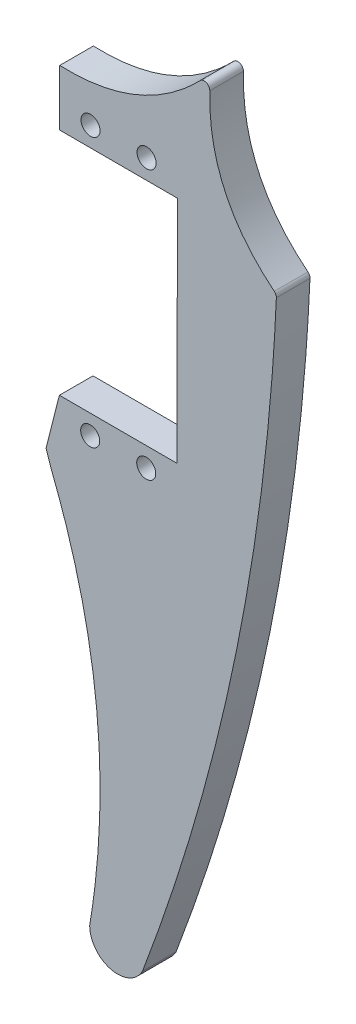
SolidWorks part; units mm, degrees
material "ABS"
ref_plane "Front Plane" through (0, 0, 0) normal (0, 0, 1) x (1, 0, 0)
ref_plane "Top Plane" through (0, 0, 0) normal (0, 1, 0) x (1, 0, 0)
ref_plane "Right Plane" through (0, 0, 0) normal (1, 0, 0) x (0, 0, -1)
sketch "Sketch1" plane through (0, 0, 0) normal (0, 0, 1) x (1, 0, 0)
  line L1 (-25, -73) -> (25, -73)
  line L2 (-25, -73) -> (-25, 73)
  line L3 (-25, 73) -> (25, 73)
  line L4 (25, -73) -> (25, 73)
  line L5 (-25, -73) -> (25, 73) construction
  line L6 (-25, 73) -> (25, -73) construction
  point P0 (0, 0)
  dimension "D1" = 50
  dimension "D2" = 146
extrude "Boss-Extrude1" add sketch "Sketch1" along normal blind 6
sketch "Sketch3" plane through (0, 0, 6) normal (0, 0, 1) x (1, 0, 0)
  line L0 (-18.1577, 62.4611) -> (-18.1698, 52.4611)
  line L1 (-18.1698, 52.4611) -> (2.8301, 52.4355)
  line L2 (2.8301, 52.4355) -> (2.7802, 11.4356)
  line L3 (2.7802, 11.4356) -> (-18.2198, 11.4611)
  line L4 (-18.2198, 11.4611) -> (-20.6029, 2.0952)
  line L5 (-25, 73) -> (25, 73)
  line L6 (25, 73) -> (25, -73)
  line L7 (25, -73) -> (-25, -73)
  line L8 (-25, -73) -> (-25, 73)
  circle A0 centre (-12.724, 7.9545) radius 1.7
  circle A1 centre (-2.724, 7.9423) radius 1.7
  circle A2 centre (-12.6656, 55.9544) radius 1.7
  circle A3 centre (-2.6656, 55.9422) radius 1.7
  arc A4 (6.9003, 72.6534) -> (8.6175, 71.93) centre (7.6179, 71.9569) cw
  arc A5 (20.1233, 46.7018) -> (20.4934, 45.8805) centre (19.4944, 45.9243) cw
  arc A6 (20.4944, 45.9231) -> (20.1233, 46.7018) centre (19.4944, 45.9243) ccw construction
  arc A7 (-12.8163, -67.7955) -> (-3.3861, -70.1197) centre (-7.8163, -67.8016) ccw
  arc A8 (-12.8163, -67.7955) -> (-3.3861, -70.1197) centre (-7.8163, -67.8016) ccw construction
  spline S0 degree 2 poles (8.6175, 71.93) (8.1984, 56.3487) (20.1233, 46.7018) knots 0.080015 0.080015 0.080015 0.985244 0.985244 0.985244 weights 1 1 1 construction
  spline S1 degree 3 poles (-20.6029, 2.0952) (-20.0205, 0.1176) (-18.5975, -3.3343) (-16.9042, -8.2632) (-15.5957, -12.5461) (-14.4561, -16.8104) (-13.503, -20.9757) (-12.4751, -26.3756) (-11.593, -32.6604) (-10.8025, -42.8899) (-11.0088, -54.6421) (-12.1531, -63.8384) (-12.8163, -67.7955) knots 0 0 0 0 0.086646 0.157135 0.219373 0.275195 0.342966 0.399252 0.506628 0.609998 0.831095 1 1 1 1
  spline S2 degree 2 poles (-20.5559, 1.4618) (-6.7301, -31.4908) (-12.8163, -67.7955) knots 0.004655 0.004655 0.004655 1 1 1 weights 1 1 1 construction
  spline S3 degree 3 poles (-3.3861, -70.1197) (-2.2175, -67.0295) (-0.1824, -61.4321) (2.3206, -54.0109) (4.3961, -47.472) (6.0842, -41.8268) (7.7734, -35.8279) (9.3145, -30.0063) (10.8472, -23.7774) (12.2485, -17.634) (13.3818, -12.2462) (14.4459, -6.8132) (15.4509, -1.2735) (16.5413, 5.3978) (17.5258, 12.2275) (18.3183, 18.5775) (18.9682, 24.556) (19.5468, 30.7474) (20.0911, 37.9797) (20.3738, 43.1533) (20.4934, 45.8805) knots 0 0 0 0 0.083335 0.150214 0.197536 0.256374 0.298828 0.354729 0.408267 0.460623 0.51366 0.547132 0.600265 0.655666 0.71763 0.774303 0.817072 0.869314 0.931145 1 1 1 1
  spline S4 degree 2 poles (20.4934, 45.8805) (17.8703, -13.9112) (-3.3861, -70.1197) knots 0.004232 0.004232 0.004232 1 1 1 weights 1 1 1 construction
  spline S5 degree 3 poles (8.6175, 71.93) (8.5907, 70.9316) (8.6162, 68.5087) (8.9751, 65.3342) (9.6754, 62.1669) (10.4078, 59.8785) (11.3756, 57.5671) (12.4767, 55.4209) (13.9857, 53.0738) (15.6991, 50.9092) (17.7271, 48.7578) (19.2236, 47.4296) (20.1233, 46.7018) knots 0 0 0 0 0.104003 0.25221 0.331596 0.441573 0.501853 0.592428 0.69239 0.791956 0.879472 1 1 1 1
  spline S6 degree 3 poles (-18.1577, 62.4611) (-16.5958, 62.4005) (-13.7728, 62.4643) (-9.6976, 63.0746) (-6.3235, 64.0142) (-3.3308, 65.2192) (-0.9448, 66.4543) (1.1131, 67.7452) (3.761, 69.6585) (5.6318, 71.3461) (6.9003, 72.6534) knots 0 0 0 0 0.167942 0.302841 0.441809 0.543311 0.649111 0.730099 0.8042 1 1 1 1
  spline S7 degree 2 poles (-18.1577, 62.4611) (-3.5411, 61.8953) (6.9003, 72.6534) knots 0 0 0 0.915673 0.915673 0.915673 weights 1 1 1 construction
  line M1 (25, -73) -> (25, 73)
  line M2 (25, 73) -> (-25, 73)
  line M3 (-25, 73) -> (-25, -73)
  line M4 (-25, -73) -> (25, -73)
extrude "Cut-Extrude1" cut sketch "Sketch3" against normal through all contours L0 S6 A4 S5 A5 S3 A7 S1 L4 L3 L2 L1 M4 M1 M2 M3 | A0 | A1 | A2 | A3 region at (0, 71.4568, 6) region at (-12.724, 7.9545, 6) region at (-2.724, 7.9423, 6) region at (-12.6656, 55.9544, 6) region at (-2.6656, 55.9422, 6)
